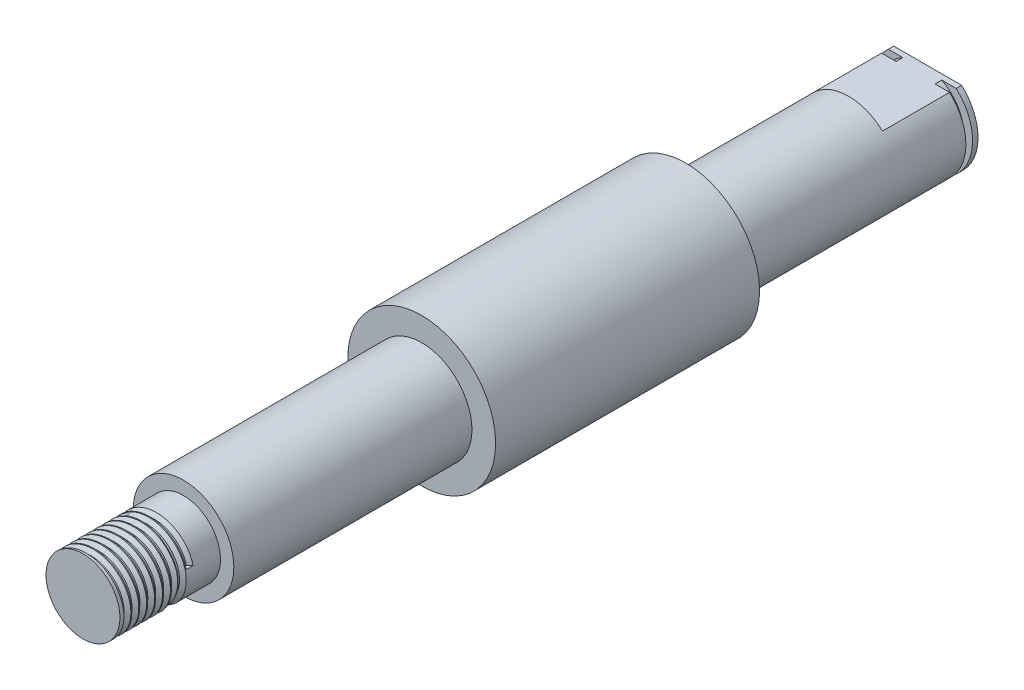
SolidWorks part; units mm, degrees
material "AISI 1020"
ref_plane "Front Plane" through (0, 0, 0) normal (0, 0, 1) x (1, 0, 0)
ref_plane "Top Plane" through (0, 0, 0) normal (0, 1, 0) x (1, 0, 0)
ref_plane "Right Plane" through (0, 0, 0) normal (1, 0, 0) x (0, 0, -1)
sketch "Sketch Spindle Skeleton" plane through (0, 0, 0) normal (1, 0, 0) x (0, 0, -1)
  line L0 (-95.847, -9.525) -> (-140.95, -9.525)
  line L5 (-1000, 0) -> (49000, 0)
  line L6 (0, -9.525) -> (0, 9.525)
  line L13 (0, 9.525) -> (-45.847, 9.525)
  line L26 (-45.847, 9.525) -> (-45.847, 14)
  line L27 (-45.847, 14) -> (-95.847, 14)
  line L32 (-95.847, 14) -> (-95.847, 9.525)
  line L34 (-160, 7) -> (-160, -7)
  line L36 (-95.847, -9.525) -> (-95.847, -14)
  line L37 (-95.847, -14) -> (-45.847, -14)
  line L38 (-45.847, -14) -> (-45.847, -9.525)
  line L39 (0, -9.525) -> (-45.847, -9.525)
  line L40 (-26.321, 36.5125) -> (-17.321, 36.5125)
  line L41 (-111.341, 22.6187) -> (-95.847, 22.6187)
  line L42 (-111.341, 22.6187) -> (-111.341, -22.6187)
  line L43 (-111.341, -22.6187) -> (-95.847, -22.6187)
  line L44 (-95.847, 22.6187) -> (-95.847, -22.6187)
  line L45 (-111.341, 22.6187) -> (-95.847, -22.6187) construction
  line L46 (-111.341, -22.6187) -> (-95.847, 22.6187) construction
  line L47 (-30.353, 22.6187) -> (-45.847, 22.6187)
  line L48 (-30.353, 22.6187) -> (-30.353, -22.6187)
  line L49 (-30.353, -22.6187) -> (-45.847, -22.6187)
  line L50 (-45.847, 22.6187) -> (-45.847, -22.6187)
  line L51 (-30.353, 22.6187) -> (-45.847, -22.6187) construction
  line L52 (-30.353, -22.6187) -> (-45.847, 22.6187) construction
  line L59 (-17.321, 36.5125) -> (-17.321, -36.5125)
  line L60 (-17.321, -36.5125) -> (-26.321, -36.5125)
  line L61 (-26.321, -22.6187) -> (-28.321, -22.6187)
  line L62 (-28.321, -22.6187) -> (-28.321, -12.5)
  line L63 (-28.321, -12.5) -> (-26.321, -12.5)
  line L64 (-26.321, -12.5) -> (-26.321, 12.5)
  line L65 (-26.321, 12.5) -> (-28.321, 12.5)
  line L66 (-28.321, 12.5) -> (-28.321, 22.6187)
  line L67 (-28.321, 22.6187) -> (-26.321, 22.6187)
  line L68 (-26.321, 22.6187) -> (-26.321, 36.5125)
  line L69 (-26.321, -22.6187) -> (-26.321, -36.5125)
  line L71 (-119.469, 36.5125) -> (-26.321, 36.5125)
  line L72 (-119.469, 36.5125) -> (-119.469, -36.5125)
  line L73 (-119.469, -36.5125) -> (-26.321, -36.5125)
  line L74 (-26.321, 36.5125) -> (-26.321, -36.5125)
  line L75 (-119.469, 36.5125) -> (-26.321, -36.5125) construction
  line L76 (-119.469, -36.5125) -> (-26.321, 36.5125) construction
  line L77 (-140.95, -9.525) -> (-140.95, -7)
  line L78 (-140.95, -7) -> (-160, -7)
  line L79 (-95.847, 9.525) -> (-140.95, 9.525)
  line L80 (-140.95, 7) -> (-160, 7)
  line L81 (-140.95, 9.525) -> (-140.95, 7)
  line L82 (-118.3985, 9.525) -> (-118.3985, -9.525) construction
  line L83 (-22.9235, 9.525) -> (-22.9235, -9.525) construction
  line L96 (-119.469, 36.5125) -> (-134.709, 36.5125)
  line L98 (-119.469, -36.5125) -> (-134.709, -36.5125)
  line L99 (-134.709, 36.5125) -> (-134.709, -36.5125)
  line L110 (-119.469, 36.5125) -> (-119.469, -36.5125)
  point P3 (0, 0)
  point P18 (-103.594, 0)
  point P24 (-38.1, 0)
  point P29 (-72.895, 0)
  point P48 (-17.321, 30.5656)
  point P70 (-134.709, 31.75)
revolve "Revolve Spindle" add sketch "Sketch Spindle Skeleton" angle 360 about L5 region at (0, 7, 70.847) region at (0, 4.7625, 103.594) region at (0, 4.7625, 115.405) region at (0, 4.7625, 38.1) region at (0, 4.7625, 127.089) region at (0, 4.7625, 28.337) region at (0, 3.8893, 146.576) region at (0, 4.7625, 21.821) region at (0, 4.7625, 8.6605)
thread "Chuck Thread" pitch 1.5 method cut profile "Thread Profile2" start angle 0, offset 0, length 12.7, pitch 1.5, diameter 14
ref_plane "Plane2" through (-7, 0, 160) normal (0, -1, 0) x (-1, 0, 0)
sketch "Thread Profile2" plane through (-7, 0, 160) normal (0, -1, 0) x (-1, 0, 0)
  line L0 (0, 0) -> (0, 1.5) construction
  line L11 (0, 0) -> (0, 1.3125)
  line L12 (0, 1.3125) -> (-0.8119, 0.8437)
  line L13 (-0.8119, 0.8437) -> (-0.8119, 0.4687)
  line L15 (-0.8119, 0.4687) -> (0, 0)
  line L17 (-0.8119, 0.6562) -> (0, 0.6562) construction
  point P2 (0, 0)
  dimension "Pitch" = 1.5
  dimension "Profile_Angle" = 60
  dimension "Profile_Land" = 0.375
  dimension "Profile_Height" = 0.8119
sketch "Thread Slot Sketch" plane through (0, 0, 0) normal (1, 0, 0) x (0, 0, -1)
  line L0 (-145.9866, 1.4554) -> (-147.2991, 1.4554) construction
  line L1 (-145.9866, 1.4554) -> (-147.2991, 1.4554)
  line L2 (-140.95, 7) -> (-148.5, 7) construction
  line L3 (-140.95, 9.525) -> (-140.95, -9.525) construction
  line L6 (-160, 7) -> (-160, -7) construction
  line L7 (-140.95, 7) -> (-146.3125, 7) construction
  circle A0 centre (-148.5, 7) radius 0.5
  dimension "D1" = 1
  dimension "D2" = 11.5
revolve "Thread Slot" cut sketch "Thread Slot Sketch" angle 360 about L5
sketch "Sketch Key" plane through (0, 0, 0) normal (0, 0, -1) x (-1, 0, 0)
  line L0 (0, 8.275) -> (0, 0) construction
  line L1 (-10, 7.025) -> (10, 7.025)
  line L2 (-10, 7.025) -> (-10, 9.525)
  line L3 (-10, 9.525) -> (10, 9.525)
  line L4 (10, 7.025) -> (10, 9.525)
  line L5 (-10, 7.025) -> (10, 9.525) construction
  line L6 (-10, 9.525) -> (10, 7.025) construction
  circle A1 centre (0, 0) radius 9.525
  circle A2 centre (0, 0) radius 9.525
  point P0 (0, 8.275)
  dimension "D2" = 20
  dimension "D3" = 2.5
  dimension "D1" = 0
extrude "Key Cut" cut sketch "Sketch Key" against normal blind 15 contours L3 L4 L1 L2
sketch "Sketch1" plane through (0, 0, 0) normal (1, 0, 0) x (0, 0, -1)
  line L0 (0, 0) -> (6.6986, 0) construction
  line L1 (0, -9.525) -> (0, 7.025) construction
  line L2 (-1.03, 9.525) -> (-2.3, 9.525)
  line L3 (-1.03, 9.525) -> (-1.03, 7.9375)
  line L4 (-1.03, 7.9375) -> (-2.3, 7.9375)
  line L5 (-2.3, 9.525) -> (-2.3, 7.9375)
  point P9 (-1.665, 7.9375)
  dimension "D1" = 2.3
  dimension "D2" = 1.27
  dimension "D3" = 9.525
  dimension "D4" = 7.9375
revolve "Cut-Revolve1" cut sketch "Sketch1" angle 360 about L0
